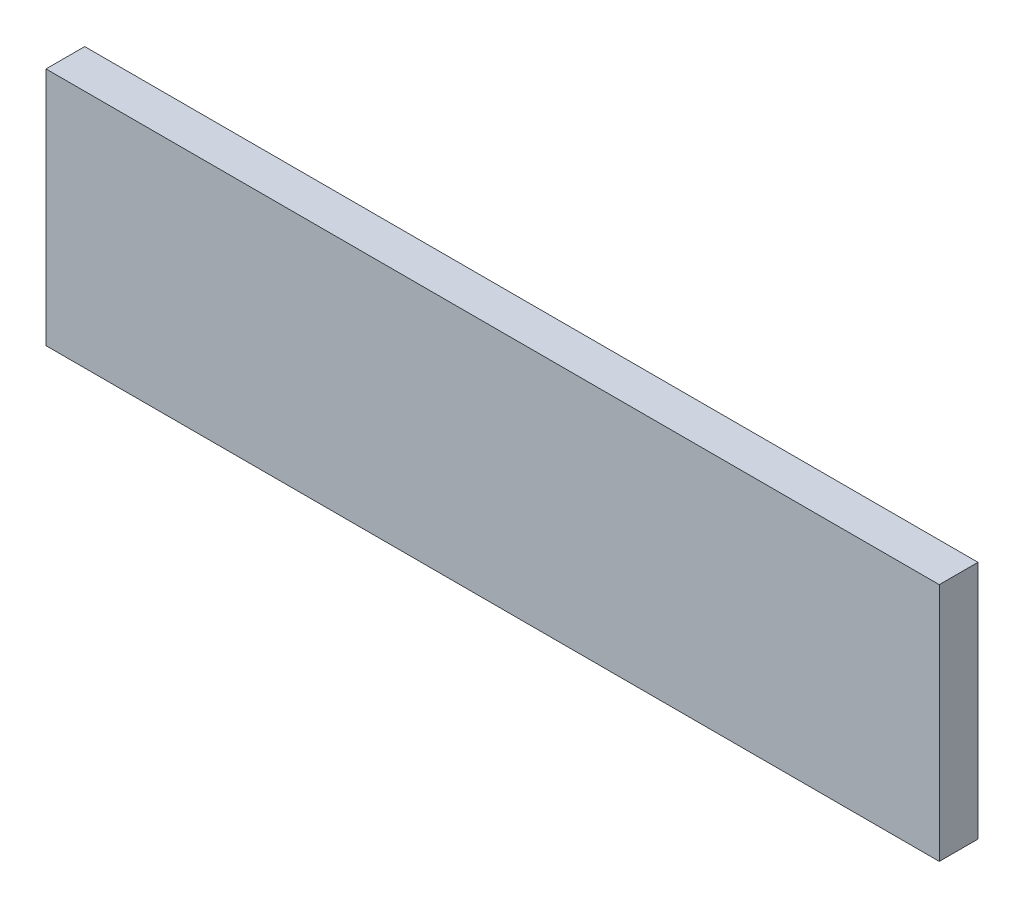
SolidWorks part; units mm, degrees
ref_plane "Plan de face" through (0, 0, 0) normal (0, 0, 1) x (1, 0, 0)
ref_plane "Plan de dessus" through (0, 0, 0) normal (0, 1, 0) x (1, 0, 0)
ref_plane "Plan de droite" through (0, 0, 0) normal (1, 0, 0) x (0, 0, -1)
sketch "Esquisse1" plane through (0, 0, 0) normal (0, 0, 1) x (1, 0, 0)
  line L1 (-36.1663, 22.3328) -> (113.8337, 22.3328)
  line L2 (-36.1663, 22.3328) -> (-36.1663, -17.9172)
  line L3 (-36.1663, -17.9172) -> (113.8337, -17.9172)
  line L4 (113.8337, 22.3328) -> (113.8337, -17.9172)
  dimension "D1" = 40.25
  dimension "D2" = 150
extrude "Boss.-Extru.1" add sketch "Esquisse1" along normal blind 6.5
